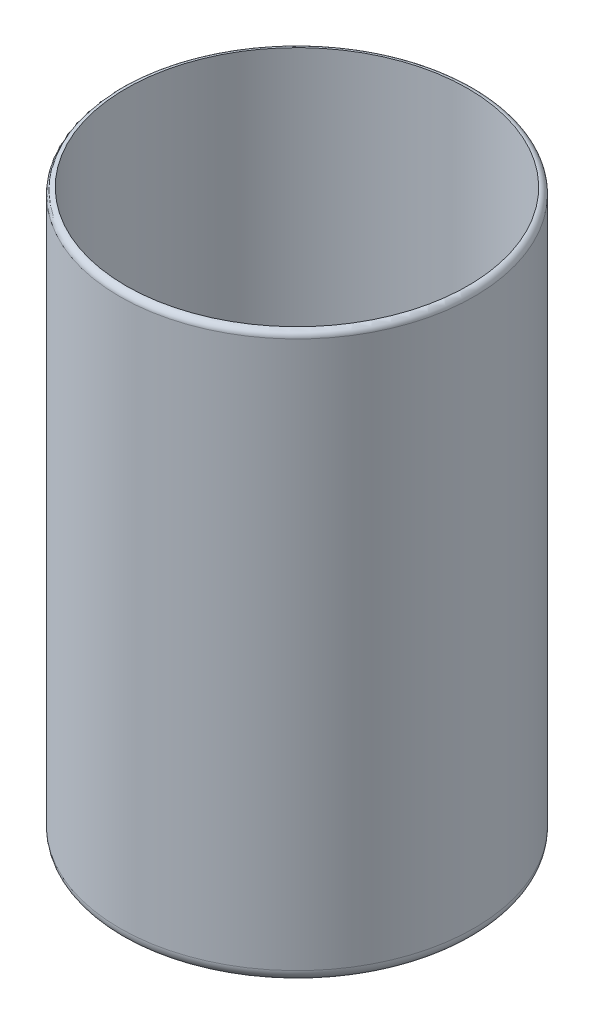
SolidWorks part; units mm, degrees
ref_plane "Front Plane" through (0, 0, 0) normal (0, 0, 1) x (1, 0, 0)
ref_plane "Top Plane" through (0, 0, 0) normal (0, 1, 0) x (1, 0, 0)
ref_plane "Right Plane" through (0, 0, 0) normal (1, 0, 0) x (0, 0, -1)
sketch "Sketch1" plane through (0, 0, 0) normal (0, 1, 0) x (1, 0, 0)
  circle A0 centre (0, 0) radius 14.25
  dimension "D1" = 28.5
extrude "Boss-Extrude1" add sketch "Sketch1" along normal blind 0.5
sketch "Sketch2" plane through (0, 0.5, 0) normal (0, 1, 0) x (1, 0, 0)
  circle A0 centre (0, 0) radius 13.75
  circle A1 centre (0, 0) radius 14.25
  circle A2 centre (0, 0) radius 14.25
  dimension "D1" = 0
  dimension "D2" = 0.5
extrude "Boss-Extrude2" add sketch "Sketch2" along normal blind 45
fillet "Fillet1" radius 1 2 edges at (0, 0, 14.25) (0, 0.5, 13.75)
fillet "Fillet2" radius 0.5 1 edges at (0, 45.5, 14.25)
